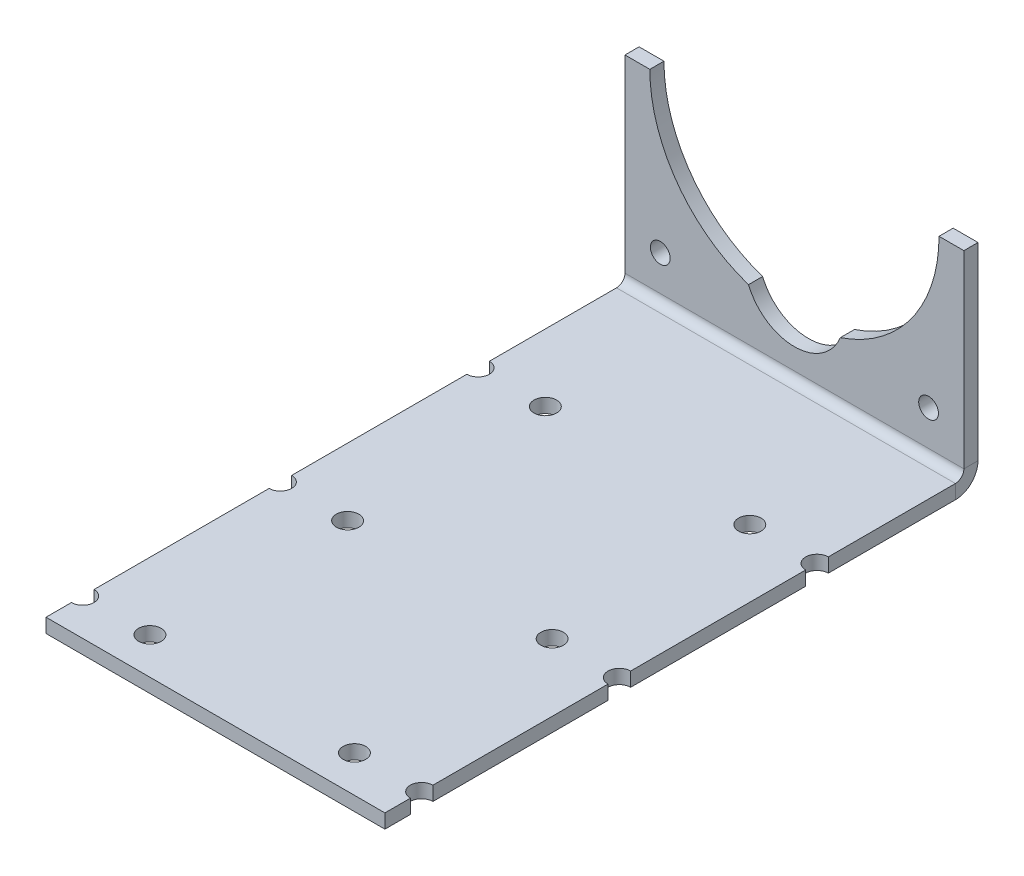
SolidWorks part; units mm, degrees
note: The reader was unsure of these and kept them because the rebuilt part matched: flange length of "Edge-Flange3".
material "1345 Alloy"
ref_plane "Front Plane" through (0, 0, 0) normal (0, 0, 1) x (1, 0, 0)
ref_plane "Top Plane" through (0, 0, 0) normal (0, 1, 0) x (1, 0, 0)
ref_plane "Right Plane" through (0, 0, 0) normal (1, 0, 0) x (0, 0, -1)
sketch "Sketch1" plane through (0, 0, 0) normal (0, 0, 1) x (1, 0, 0)
  line L27 (60, -19.74) -> (60, 100.5)
  line L28 (-60, -19.74) -> (-60, 100.5)
  line L29 (-54, 106.5) -> (54, 106.5)
  line L30 (-60, -19.74) -> (60, -19.74)
  arc A2 (60, 100.5) -> (54, 106.5) centre (54, 100.5) ccw
  arc A3 (-54, 106.5) -> (-60, 100.5) centre (-54, 100.5) ccw
  point P0 (0, 0)
  point P22 (60, 106.5)
  dimension "D1" = 126.24
base flange "Base-Flange2" sketch "Sketch1" thickness 5 reverse thickness direction yes parameters "D1"=0.7366
edge flange "Edge-Flange3" sketch "Sketch17" flange angle 90 flange length 210 flange position material outside bend radius 3 thickness 5 parameters "D6"=10
sketch "Sketch17" plane through (0, -19.74, 5) normal (0, -1, 0) x (1, 0, 0)
  line L2 (-60, 0) -> (-60, 205)
  line L3 (-60, 205) -> (60, 205)
  line L4 (60, 205) -> (60, 0)
  line L7 (-60, 0) -> (60, 0) construction
  line L8 (-60, 0) -> (60, 0)
bend "EdgeBend3" bend radius 3 bend angle 90 parameters "D5"=1
sketch "Sketch18" plane through (0, 0, 5) normal (0, 0, 1) x (1, 0, 0)
  line L0 (-60, 100.5) -> (-60, -16.74) construction
  circle A2 centre (-50, 96.5) radius 3
  circle A3 centre (50, 96.5) radius 3
  dimension "D1" = 6
  dimension "D2" = 6
  dimension "D3" = 10
  dimension "D4" = 10
  dimension "D5" = 10
  dimension "D6" = 10
extrude "Cut-Extrude7" cut sketch "Sketch18" against normal blind 10
sketch "Sketch22" plane through (0, -19.74, 0) normal (0, 1, 0) x (1, 0, 0)
  line L0 (0, 0) -> (0, -57) construction
  line L1 (0, -57) -> (36.205, -57) construction
  line L2 (0, -57) -> (-36.205, -57) construction
  circle A0 centre (36.205, -197) radius 4
  circle A1 centre (-36.205, -197) radius 4
  circle A2 centre (-36.205, -127) radius 4
  circle A3 centre (36.205, -127) radius 4
  circle A4 centre (36.205, -57) radius 4
  circle A5 centre (-36.205, -57) radius 4
  circle A6 centre (60, -197) radius 4
  circle A7 centre (60, -127) radius 4
  circle A8 centre (-60, -197) radius 4
  circle A9 centre (-60, -127) radius 4
  circle A10 centre (-60, -57) radius 4
  circle A11 centre (60, -57) radius 4
  dimension "D1" = 8
  dimension "D2" = 8
  dimension "D3" = 8
  dimension "D4" = 8
  dimension "D5" = 57
  dimension "D6" = 36.205
  dimension "D7" = 36.205
extrude "Cut-Extrude11" cut sketch "Sketch22" against normal blind 10
sketch "Sketch25" plane through (0, 0, 0) normal (0, 0, -1) x (-1, 0, 0)
  arc A0 (16.2558, 1.6191) -> (-16.2558, 1.6191) centre (0, 50.17) ccw
  circle A1 centre (-47.5, -4.24) radius 3.5
  circle A2 centre (47.5, -4.24) radius 3.5
  arc A5 (-16.2558, 1.6191) -> (16.2558, 1.6191) centre (0, 8.26) ccw
  dimension "D1" = 102.4
  dimension "D5" = 7
  dimension "D6" = 7
  dimension "D7" = 35.12
  dimension "D2" = 54.41
  dimension "D3" = 95
  dimension "D4" = 47.5
extrude "Cut-Extrude14" cut sketch "Sketch25" against normal blind 10
sketch "Sketch26" plane through (0, 0, 0) normal (0, 0, -1) x (-1, 0, 0)
  line L0 (-51.2, 50.17) -> (-60, 50.17)
  line L1 (-51.2, 50.17) -> (-0.725, 50.17)
  line L2 (-60, -16.74) -> (-60, 100.5) construction
  line L3 (-60, 50.17) -> (-60, 106.5)
  line L4 (-60, 106.5) -> (60, 106.5)
  line L5 (60, 106.5) -> (60, 50.17)
  line L6 (60, 100.5) -> (60, -16.74) construction
  line L7 (60, 50.17) -> (0, 50.17)
  arc A0 (16.2558, 1.6191) -> (-16.2558, 1.6191) centre (0, 50.17) ccw construction
extrude "Cut-Extrude17" cut sketch "Sketch26" against normal through all and the other way through all
sketch "Bend-Lines5" [suppressed] plane through (0, 0, 0) normal (0, 1, 0) x (1, 0, 0)
sketch "Bounding-Box5" [suppressed] plane through (0, 0, 0) normal (0, 1, 0) x (1, 0, 0)
sheet metal parameters "Sheet-Metal14" thickness 5 parameters "D1"=0.7366
flat pattern "Flat-Pattern14" [suppressed]
sketch "Bend-Lines6" plane through (0, 0, 0) normal (0, 0, -1) x (-1, 0, 0)
sketch3d "Bounding-Box6" [suppressed]
  line L0 (-6, -143, 0) -> (-6, 6, 0) construction
  line L1 (114, -143, 0) -> (114, 6, 0) construction
  line L2 (-6, -143, 0) -> (114, -143, 0) construction
  line L3 (-6, 6, 0) -> (114, 6, 0) construction
sketch "Sketch11-1" [suppressed] plane through (0, 0, 5) normal (0, 0, 1) x (1, 0, 0)
  line L1 (0, 106.5) -> (0, -30.5934) construction
  line L4 (-60, -30.5934) -> (60, -30.5934)
sheet metal parameters "Sheet-Metal16" thickness 5 parameters "D1"=0.7366
flat pattern "Flat-Pattern14"
sketch "Bend-Lines6" plane through (0, 0, 0) normal (0, 0, -1) x (-1, 0, 0)
  line L0 (-60, -44.3054) -> (60, -44.3054) construction
  line L1 (-60, -44.3054) -> (60, -44.3054) construction
sketch3d "Bounding-Box6" [suppressed]
  line L0 (-6, -192.6108, 0) -> (-6, 6, 0) construction
  line L1 (114, -192.6108, 0) -> (114, 6, 0) construction
  line L2 (-6, -192.6108, 0) -> (114, -192.6108, 0) construction
  line L3 (-6, 6, 0) -> (114, 6, 0) construction
bend of the flat pattern "Flatten-<EdgeBend3>1"
sheet metal parameters "Sheet-Metal17" thickness 5 parameters "D1"=0.7366
flat pattern "Flat-Pattern14"
sketch "Bend-Lines6" plane through (0, 0, 0) normal (0, 0, -1) x (-1, 0, 0)
  line L0 (-60, -44.3054) -> (60, -44.3054) construction
  line L1 (-60, -44.3054) -> (60, -44.3054) construction
sketch3d "Bounding-Box6" [suppressed]
  line L0 (-6, -192.6108, 0) -> (-6, 6, 0) construction
  line L1 (114, -192.6108, 0) -> (114, 6, 0) construction
  line L2 (-6, -192.6108, 0) -> (114, -192.6108, 0) construction
  line L3 (-6, 6, 0) -> (114, 6, 0) construction
bend of the flat pattern "Flatten-<EdgeBend3>1"
sheet metal parameters "Sheet-Metal21" thickness 5 parameters "D1"=0.7366
flat pattern "Flat-Pattern14"
sketch "Bend-Lines6" plane through (0, 0, 0) normal (0, 0, -1) x (-1, 0, 0)
  line L0 (-60, -20.3171) -> (60, -20.3171) construction
  line L1 (-60, -20.3171) -> (60, -20.3171) construction
sketch3d "Bounding-Box6" [suppressed]
  line L0 (-6, -326.3942, 0) -> (-6, 6, 0) construction
  line L1 (114, -326.3942, 0) -> (114, 6, 0) construction
  line L2 (-6, -326.3942, 0) -> (114, -326.3942, 0) construction
  line L3 (-6, 6, 0) -> (114, 6, 0) construction
bend of the flat pattern "Flatten-<EdgeBend3>1"
sheet metal parameters "Sheet-Metal25" thickness 5 parameters "D1"=0.7366
flat pattern "Flat-Pattern14"
sketch "Bend-Lines6" plane through (0, 0, 0) normal (0, 0, -1) x (-1, 0, 0)
  line L0 (-60, -20.3171) -> (60, -20.3171) construction
  line L1 (-60, -20.3171) -> (60, -20.3171) construction
sketch3d "Bounding-Box6" [suppressed]
  line L0 (-6, -326.3942, 0) -> (-6, 6, 0) construction
  line L1 (114, -326.3942, 0) -> (114, 6, 0) construction
  line L2 (-6, -326.3942, 0) -> (114, -326.3942, 0) construction
  line L3 (-6, 6, 0) -> (114, 6, 0) construction
bend of the flat pattern "Flatten-<EdgeBend3>1"
sheet metal parameters "Sheet-Metal26" thickness 5 parameters "D1"=0.7366
flat pattern "Flat-Pattern14"
sketch "Bend-Lines6" plane through (0, 0, 0) normal (0, 0, -1) x (-1, 0, 0)
  line L0 (-60, -20.3171) -> (60, -20.3171) construction
  line L1 (-60, -20.3171) -> (60, -20.3171) construction
sketch3d "Bounding-Box6" [suppressed]
  line L0 (-6, -50.33, 0) -> (-6, -326.3942, 0) construction
  line L1 (114, -50.33, 0) -> (114, -326.3942, 0) construction
  line L2 (-6, -50.33, 0) -> (114, -50.33, 0) construction
  line L3 (-6, -326.3942, 0) -> (114, -326.3942, 0) construction
bend of the flat pattern "Flatten-<EdgeBend3>1"
